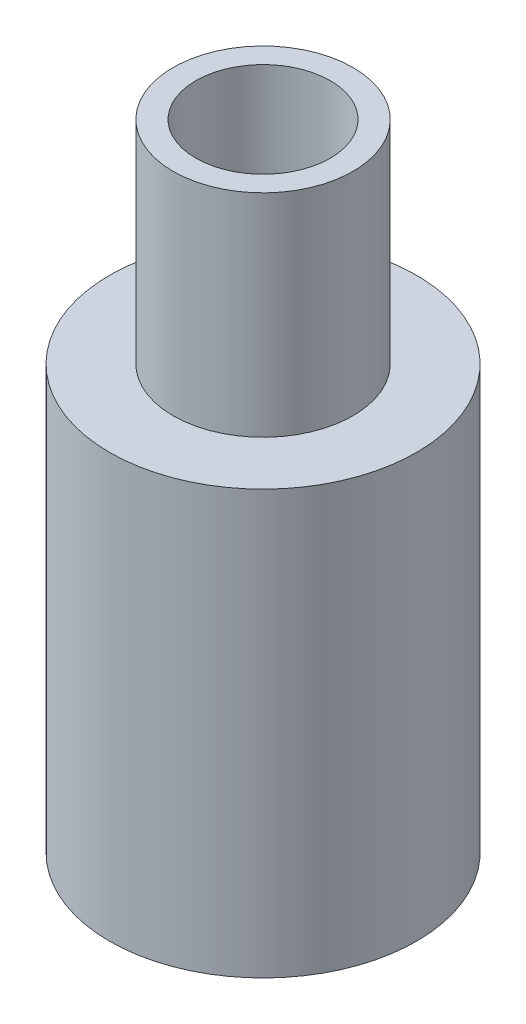
SolidWorks part; units mm, degrees
ref_plane "Front Plane" through (0, 0, 0) normal (0, 0, 1) x (1, 0, 0)
ref_plane "Top Plane" through (0, 0, 0) normal (0, 1, 0) x (1, 0, 0)
ref_plane "Right Plane" through (0, 0, 0) normal (1, 0, 0) x (0, 0, -1)
sketch "Sketch1" plane through (0, 0, 0) normal (0, 1, 0) x (1, 0, 0)
  circle A0 centre (0, 0) radius 3.175
  circle A1 centre (0, 0) radius 7.25
  dimension "D1" = 6.35
  dimension "D2" = 14.5
extrude "Boss-Extrude1" add sketch "Sketch1" along normal blind 30
sketch "Sketch2" plane through (0, 30, 0) normal (0, 1, 0) x (1, 0, 0)
  circle A0 centre (0, 0) radius 4.25
  dimension "D1" = 8.5
extrude "Cut-Extrude1" cut sketch "Sketch2" against normal blind 10 flip side to cut
sketch "Sketch3" plane through (0, 0, 0) normal (0, -1, 0) x (1, 0, 0)
  circle A1 centre (0, 0) radius 4.25
  dimension "D1" = 8.5
extrude "Cut-Extrude2" cut sketch "Sketch3" against normal blind 9
